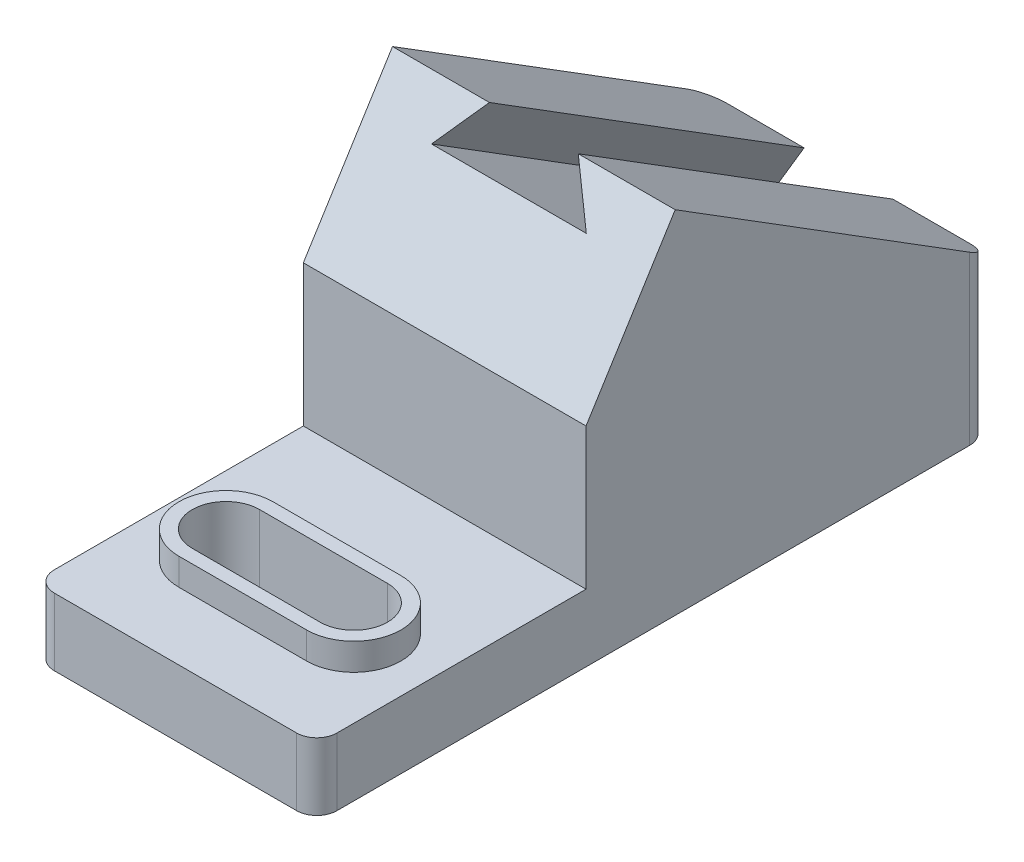
SolidWorks part; units mm, degrees
ref_plane "Front Plane" through (0, 0, 0) normal (0, 0, 1) x (1, 0, 0)
ref_plane "Top Plane" through (0, 0, 0) normal (0, 1, 0) x (1, 0, 0)
ref_plane "Right Plane" through (0, 0, 0) normal (1, 0, 0) x (0, 0, -1)
sketch "Sketch1" plane through (0, 0, 0) normal (1, 0, 0) x (0, 0, -1)
  line L0 (0, 0) -> (0, 22.9873)
  line L1 (0, 22.9873) -> (-46.752, 52.2012)
  line L2 (-46.752, 52.2012) -> (-60, 31)
  line L3 (-60, 31) -> (-60, 10)
  line L4 (-60, 10) -> (-100, 10)
  line L5 (-100, 10) -> (-100, 0)
  line L6 (-100, 0) -> (0, 0)
  line L7 (0, 22.9873) -> (-28.2692, 22.9873) construction
  dimension "D1" = 60
  dimension "D2" = 32
  dimension "D3" = 25
  dimension "D4" = 31
  dimension "D5" = 100
  dimension "D6" = 10
extrude "Boss-Extrude1" add sketch "Sketch1" along normal mid plane 42
sketch "Sketch2" plane through (0, 10, 0) normal (0, 1, 0) x (1, 0, 0)
  line L0 (-9.5, -83) -> (9.5, -83) construction
  line L1 (-9.5, -76) -> (9.5, -76)
  line L2 (-9.5, -90) -> (9.5, -90)
  line L3 (21, -100) -> (-21, -100) construction
  line L4 (-9.5, -78) -> (9.5, -78)
  line L5 (-9.5, -88) -> (9.5, -88)
  line L6 (21, -100) -> (-21, -100)
  arc A0 (-9.5, -76) -> (-9.5, -90) centre (-9.5, -83) ccw
  arc A5 (9.5, -90) -> (9.5, -76) centre (9.5, -83) ccw
  arc A6 (9.5, -88) -> (9.5, -78) centre (9.5, -83) ccw
  arc A7 (-9.5, -78) -> (-9.5, -88) centre (-9.5, -83) ccw
  point P2 (0, -83)
  point P11 (0, 0)
  point P16 (0, -83)
  point P17 (0, -100)
  dimension "D1" = 17
  dimension "D3" = 7
  dimension "D2" = 19
  dimension "D4" = 2
extrude "Boss-Extrude2" add sketch "Sketch2" along normal blind 4 contours L2 A5 L1 A0 A7 L4 A6 L5 region at (0, 10, 76.3585)
extrude "Cut-Extrude1" cut sketch "Sketch2<3>" against normal through all contours L4 A7 L5 A6 region at (0, 10, 83)
sketch "Sketch2<3>" plane through (0, 10, 0) normal (0, 1, 0) x (1, 0, 0) same geometry as "Sketch2"
sketch "Sketch3" plane through (0, 35.6691, 57.0824) normal (0, 0.5299, 0.848) x (1, 0, 0)
  line L0 (-21, -5.5057) -> (-21, 19.4943)
  line L1 (-21, 19.4943) -> (-6.5985, 19.4943)
  line L2 (21, 19.4943) -> (-21, 19.4943) construction
  line L3 (-6.5985, 19.4943) -> (-11.5, 12.4943)
  line L4 (-11.5, 12.4943) -> (11.5, 12.4943)
  line L5 (11.5, 12.4943) -> (6.5985, 19.4943)
  line L6 (6.5985, 19.4943) -> (21, 19.4943)
  line L7 (21, 19.4943) -> (21, -5.5057)
  line L8 (21, -5.5057) -> (-21, -5.5057)
  line L9 (0, -5.5057) -> (0, 19.4943) construction
  line L10 (-6.5985, 19.4943) -> (6.5985, 19.4943)
  line M4 (21, 19.4943) -> (-21, 19.4943)
  dimension "D1" = 23
  dimension "D2" = 55
  dimension "D3" = 7
extrude "Cut-Extrude2" cut sketch "Sketch3" against normal up to surface (55.129 mm away) contours L9 L4 L5 M4 | L4 L9 L10 L3 region at (-4.6353, 48.9651, 48.7742) region at (4.6353, 48.9651, 48.7742) up to face at (0, 11.4936, 0)
fillet "Fillet1" radius 3 4 edges at (-21, 11.4936, 0) (21, 11.4936, 0) (-21, 5, 100) (21, 5, 100)
